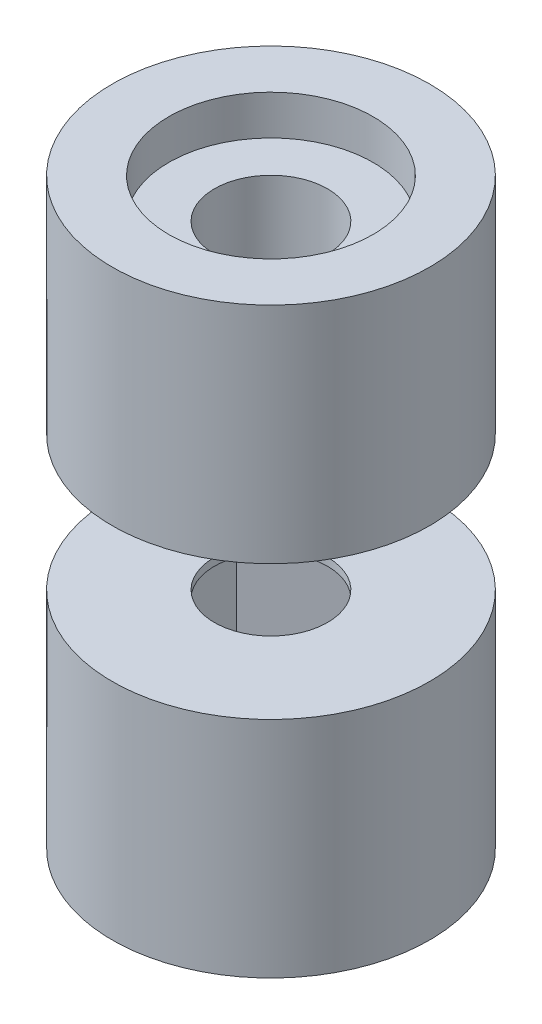
SolidWorks part; units mm, degrees
ref_plane "Front Plane" through (0, 0, 0) normal (0, 0, 1) x (1, 0, 0)
ref_plane "Top Plane" through (0, 0, 0) normal (0, 1, 0) x (1, 0, 0)
ref_plane "Right Plane" through (0, 0, 0) normal (1, 0, 0) x (0, 0, -1)
sketch "Sketch1" plane through (0, 0, 0) normal (0, 1, 0) x (1, 0, 0)
  circle A0 centre (0, 0) radius 8
extrude "Boss-Extrude1" add sketch "Sketch1" along normal blind 29.381
sketch "Sketch2" plane through (0, 0, 0) normal (0, 0, 1) x (1, 0, 0)
  line L0 (-10.2, 11.29) -> (10.2, 11.29)
  line L1 (10.2, 11.29) -> (10.2, 18.09)
  line L2 (10.2, 18.09) -> (-10.2, 18.09)
  line L3 (-10.2, 18.09) -> (-10.2, 11.29)
extrude "Cut-Extrude1" cut sketch "Sketch2" against normal through all and the other way through all
sketch "Sketch3" plane through (0, 0, 0) normal (0, 1, 0) x (1, 0, 0)
  circle A0 centre (0, 0) radius 2.85
extrude "Cut-Extrude2" cut sketch "Sketch3" along normal blind 29.381
ref_plane "Plane1" through (0, 29.381, 0) normal (0, 1, 0) x (1, 0, 0)
sketch "Sketch4" plane through (0, 29.381, 0) normal (0, 1, 0) x (1, 0, 0)
  circle A0 centre (0, 0) radius 5.15
extrude "Cut-Extrude3" cut sketch "Sketch4" against normal blind 2
sketch "Sketch5" plane through (0, 0, 0) normal (0, 1, 0) x (1, 0, 0)
  line L0 (4.1, -2.3671) -> (0, -4.7343)
  line L1 (0, -4.7343) -> (-4.1, -2.3671)
  line L2 (-4.1, -2.3671) -> (-4.1, 2.3671)
  line L3 (-4.1, 2.3671) -> (0, 4.7343)
  line L4 (0, 4.7343) -> (4.1, 2.3671)
  line L5 (4.1, 2.3671) -> (4.1, -2.3671)
extrude "Cut-Extrude4" cut sketch "Sketch5" along normal blind 10.9
